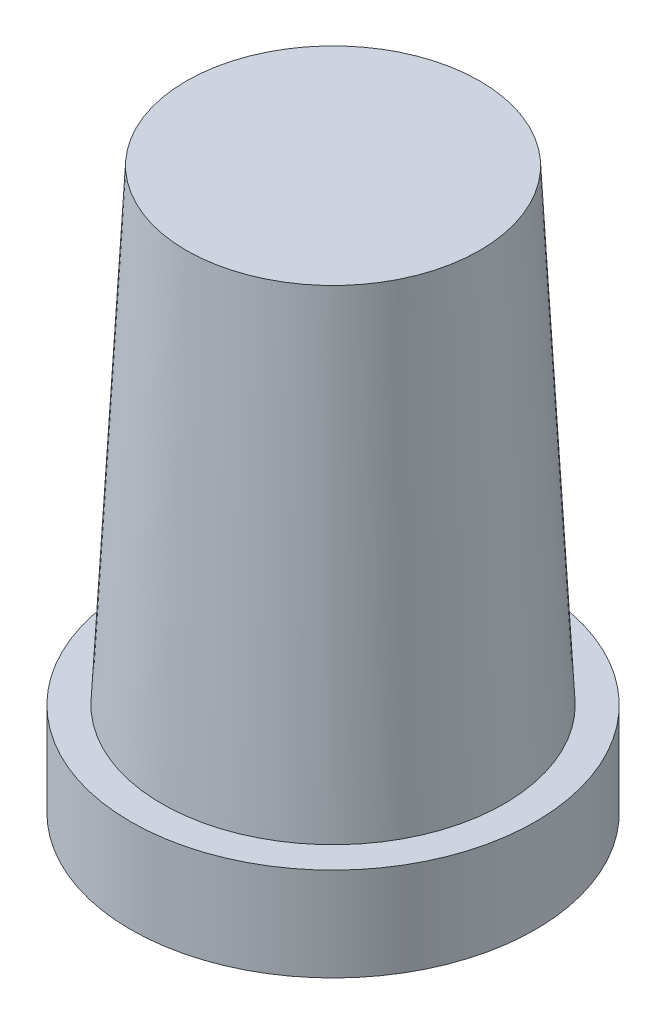
SolidWorks part; units mm, degrees
ref_plane "Спереди" through (0, 0, 0) normal (0, 0, 1) x (1, 0, 0)
ref_plane "Сверху" through (0, 0, 0) normal (0, 1, 0) x (1, 0, 0)
ref_plane "Справа" through (0, 0, 0) normal (1, 0, 0) x (0, 0, -1)
sketch "Sketch1" plane through (0, 0, 0) normal (0, 1, 0) x (1, 0, 0)
  circle A0 centre (0, 0) radius 6.5
  dimension "D1" = 13
extrude "Boss-Extrude1" add sketch "Sketch1" along normal blind 18
sketch "Sketch2" plane through (0, 0, 0) normal (0, -1, 0) x (1, 0, 0)
  circle A0 centre (0, 0) radius 5
  dimension "D1" = 10
extrude "Cut-Extrude1" cut sketch "Sketch2" against normal blind 4
sketch "Sketch3" plane through (0, 4, 0) normal (0, -1, 0) x (1, 0, 0)
  line L0 (-1.7321, -2.571) -> (3.0483, -0.5639)
  line L1 (0.6581, -1.5674) -> (-1.2001, 2.8583) construction
  circle A0 centre (0, 0) radius 3.1 construction
  arc A1 (-1.7321, -2.571) -> (3.0483, -0.5639) centre (0, 0) cw
  dimension "D1" = 6.2
  dimension "D2" = 4.8
extrude "Cut-Extrude2" cut sketch "Sketch3" against normal blind 12
chamfer "Chamfer1" distance 1 angle 30 1 edges at (0, 0, -5) first distance on face at (0, 4, -5)
sketch "Sketch4" plane through (0, 18, 0) normal (0, 1, 0) x (1, 0, 0)
  circle A0 centre (0, 0) radius 5.5
  dimension "D1" = 11
extrude "Cut-Extrude3" cut sketch "Sketch4" against normal blind 15 flip side to cut
chamfer "Chamfer2" distance 15 angle 3 1 edges at (0, 18, 5.5) first distance on face at (0, 3, 5.5)
